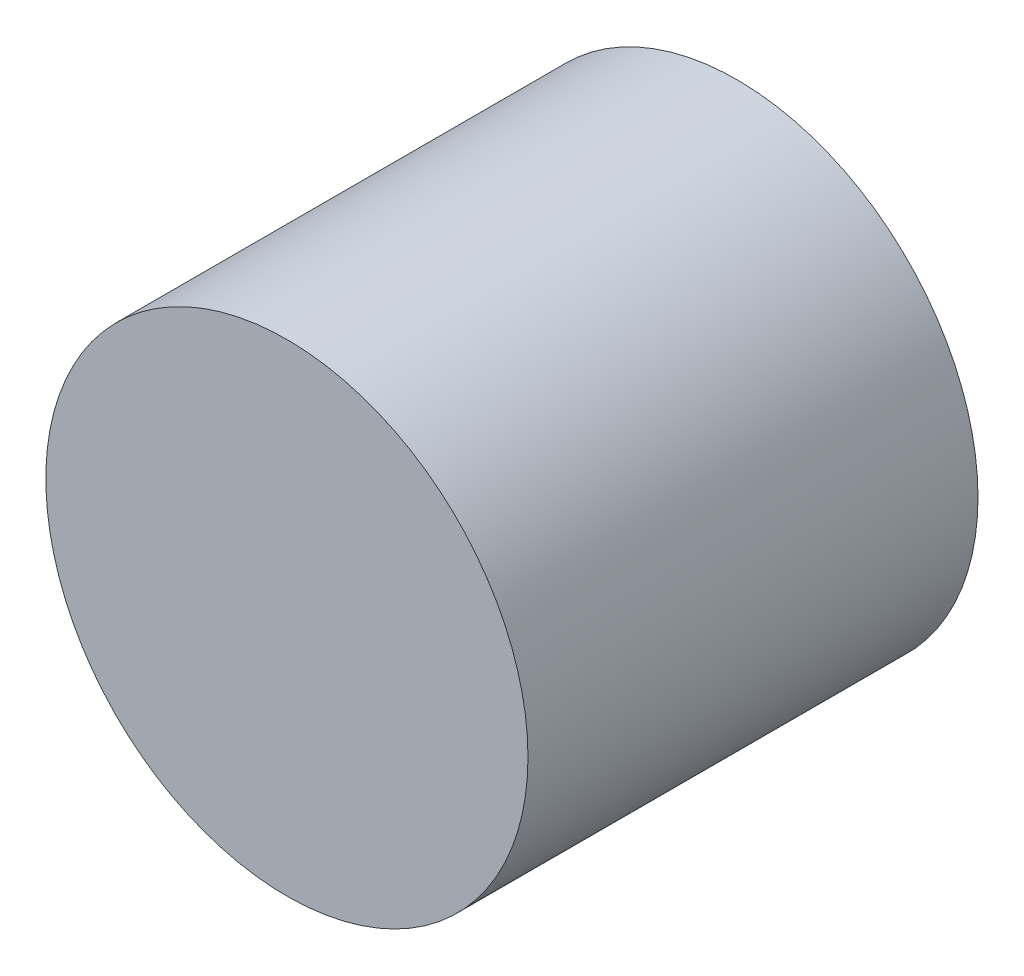
SolidWorks part; units mm, degrees
ref_plane "Front Plane" through (0, 0, 0) normal (0, 0, 1) x (1, 0, 0)
ref_plane "Top Plane" through (0, 0, 0) normal (0, 1, 0) x (1, 0, 0)
ref_plane "Right Plane" through (0, 0, 0) normal (1, 0, 0) x (0, 0, -1)
sketch "Sketch1" plane through (0, 0, 0) normal (0, 0, 1) x (1, 0, 0)
  line L0 (1000, 0) -> (7, 0) construction
  line L5 (-7, 7.5) -> (7, -7.5) construction
  line L7 (-7, 0) -> (-50000, 0) construction
  circle A0 centre (0, 0) radius 7.5
  point P0 (0, 0)
  dimension "D1" = 15
extrude "Boss-Extrude1" add sketch "Sketch1" along normal mid plane 14
hole_wizard "M8x1.0 Tapped Hole2" positions "Sketch7" profile "Sketch8" tap size "M8x1.0" standard "ANSI Metric"
sketch "Sketch7" plane through (0, 0, -7) normal (0, 0, -1) x (-1, 0, 0)
  point P0 (0, 0)
sketch "Sketch8" plane through (0, 0, -7) normal (1, 0, 0) x (0, 1, 0)
  line L0 (0, 0) -> (0, 11.103)
  line L1 (0, 11.103) -> (3.5, 9)
  line L2 (3.5, 9) -> (3.5, 0)
  line L5 (3.5, 0) -> (0, 0)
  line L10 (0, 11.103) -> (-3.5, 9) construction
  line L11 (0, -6.35) -> (0, 107.95) construction
  dimension "Tap Drill Dia." = 7
  dimension "Tap Drill Depth" = 9
  dimension "Drill Angle" = 118
cosmetic thread "Hole Thread2" parameters "D1"=16, "D2"=8
thread "Thread1" pitch 1 method cut profile "Thread Profile1" start angle 0, offset 2, length 10, pitch 1, diameter 7
ref_plane "Plane1" through (3.5, 0, -9) normal (0, 1, 0) x (-1, 0, 0)
sketch "Thread Profile1" plane through (3.5, 0, -9) normal (0, 1, 0) x (-1, 0, 0)
  line L0 (0, 0) -> (0, 1) construction
  line L11 (0, 0) -> (0, 0.875)
  line L12 (0, 0.875) -> (-0.5413, 0.5625)
  line L13 (-0.5413, 0.5625) -> (-0.5413, 0.3125)
  line L15 (-0.5413, 0.3125) -> (0, 0)
  line L17 (-0.5413, 0.4375) -> (0, 0.4375) construction
  point P2 (0, 0)
  dimension "Pitch" = 1
  dimension "Profile_Angle" = 60
  dimension "Profile_Land" = 0.25
  dimension "Profile_Height" = 0.5413
